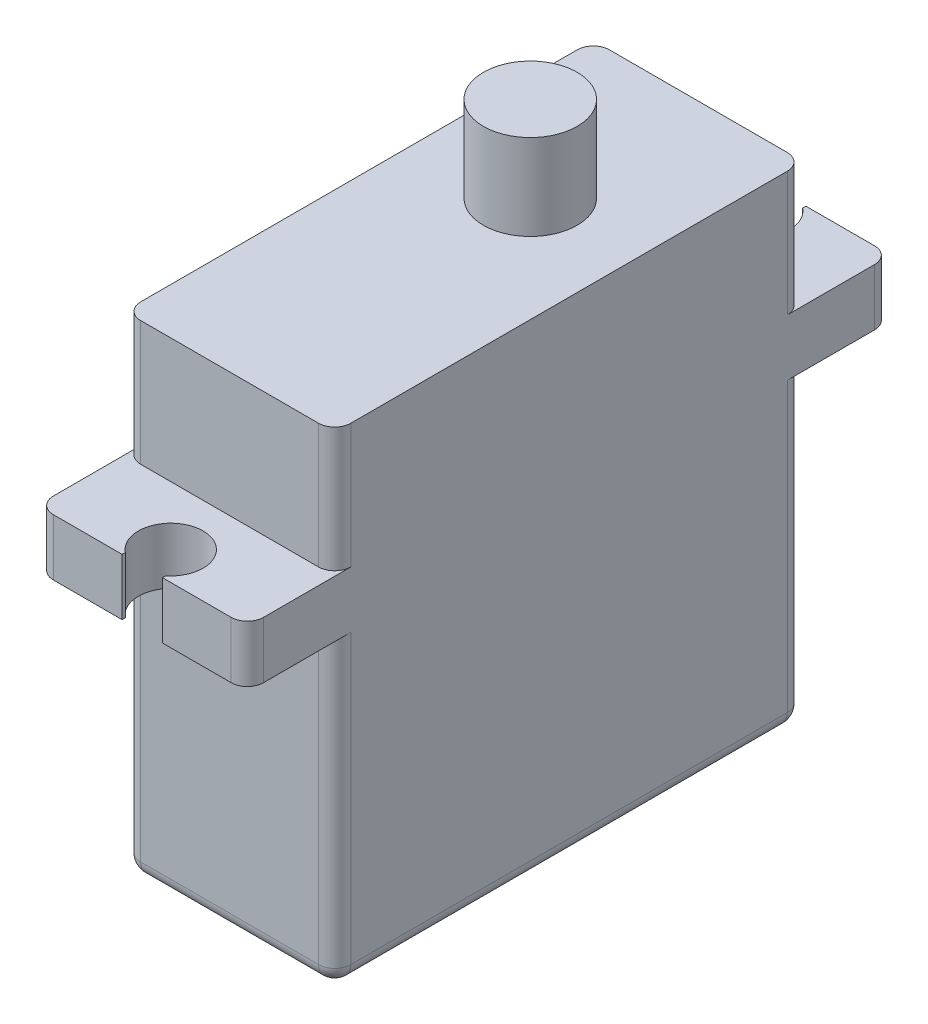
SolidWorks part; units mm, degrees
note: The reader was unsure of these and kept them because the rebuilt part matched: shared geometry of "Sketch3<4>".
ref_plane "Front Plane" through (0, 0, 0) normal (0, 0, 1) x (1, 0, 0)
ref_plane "Top Plane" through (0, 0, 0) normal (0, 1, 0) x (1, 0, 0)
ref_plane "Right Plane" through (0, 0, 0) normal (1, 0, 0) x (0, 0, -1)
sketch "Sketch2" plane through (0, 0, 0) normal (1, 0, 0) x (0, 0, -1)
  line L1 (-14.5, 15) -> (14.5, 15)
  line L2 (-14.5, 15) -> (-14.5, -15)
  line L3 (-14.5, -15) -> (14.5, -15)
  line L4 (14.5, 15) -> (14.5, -15)
  line L5 (-14.5, 15) -> (14.5, -15) construction
  line L6 (-14.5, -15) -> (14.5, 15) construction
  line L7 (14.5, 7.3) -> (19.9, 7.3)
  line L8 (14.5, 7.3) -> (14.5, 3.8)
  line L9 (14.5, 3.8) -> (19.9, 3.8)
  line L10 (19.9, 7.3) -> (19.9, 3.8)
  line L11 (-14.5, 7.3) -> (-19.9, 7.3)
  line L12 (-14.5, 7.3) -> (-14.5, 3.8)
  line L13 (-14.5, 3.8) -> (-19.9, 3.8)
  line L14 (-19.9, 7.3) -> (-19.9, 3.8)
  line L16 (-19.9, 5.55) -> (19.9, 5.55) construction
  line L17 (1.2, 15) -> (7, 15)
  line L18 (1.2, 15) -> (1.2, 20.3)
  line L19 (1.2, 20.3) -> (7, 20.3)
  line L20 (7, 15) -> (7, 20.3)
  point P0 (0, 0)
  point P22 (0, 5.55)
  dimension "D1" = 22.3
  dimension "D2" = 29
  dimension "D3" = 35.3
  dimension "D4" = 39.8
  dimension "D5" = 30
  dimension "D6" = 3.5
  dimension "D7" = 5.8
  dimension "D8" = 7.5
extrude "Boss-Extrude1" add sketch "Sketch2" along normal blind 13 contours L4 L1 L2 L3 | L11 L14 L13 L2 | L1 L20 L19 L18 | L10 L7 L4 L9
sketch "Sketch3" plane through (0, 15, 0) normal (0, 1, 0) x (1, 0, 0)
  line L0 (13, 7) -> (0, 7) construction
  line L1 (13, 1.2) -> (9.4, 1.2)
  line L2 (13, 1.2) -> (13, 7)
  line L3 (13, 7) -> (9.4, 7)
  line L4 (9.4, 1.2) -> (9.4, 7)
  line L5 (13, 7) -> (0, 7) construction
  line L6 (0, 1.2) -> (3.6, 1.2)
  line L7 (0, 1.2) -> (0, 7)
  line L8 (0, 7) -> (3.6, 7)
  line L9 (3.6, 1.2) -> (3.6, 7)
  line L10 (13, 19.9) -> (0, 19.9) construction
  line L11 (9.4, 7) -> (3.6, 7)
  line L12 (9.4, 1.2) -> (3.6, 1.2)
  line L15 (13, -19.9) -> (0, -19.9) construction
  line L16 (7.75, 19.9) -> (7.75, 19.7)
  line L17 (5.25, 19.9) -> (5.25, 19.7)
  line L18 (7.75, 19.9) -> (5.25, 19.9)
  line L21 (7.75, -19.9) -> (7.75, -19.7)
  line L22 (7.75, -19.9) -> (5.25, -19.9)
  line L23 (5.25, -19.9) -> (5.25, -19.7)
  circle A0 centre (6.5, 4.1) radius 2.9
  arc A1 (5.25, 19.7) -> (7.75, 19.7) centre (6.5, 18.1388) ccw
  arc A2 (7.75, -19.7) -> (5.25, -19.7) centre (6.5, -18.1388) ccw
  point P15 (3.6, 4.1)
  point P21 (6.5, 19.9)
  dimension "D1" = 4
  dimension "D2" = 2.5
  dimension "D3" = 0.2
extrude "Cut-Extrude1" cut sketch "Sketch3" along normal up to surface (5.3 mm away)
extrude "Cut-Extrude2" cut sketch "Sketch3<4>" against normal through all
sketch "Sketch3<4>" plane through (0, 15, 0) normal (0, 1, 0) x (1, 0, 0) same geometry as "Sketch3"
fillet "Fillet1" radius 1 16 edges at (0, 5.55, 19.9) (13, 5.55, 19.9) (0, 11.15, -14.5) (13, 11.15, -14.5) (6.5, -15, -14.5) (0, -15, 0) (6.5, -15, 14.5) (0, -5.6, 14.5) (13, -5.6, 14.5) (0, 11.15, 14.5) (13, 11.15, 14.5) (13, -15, 0) (0, -5.6, -14.5) (13, -5.6, -14.5) (0, 5.55, -19.9) (13, 5.55, -19.9)
